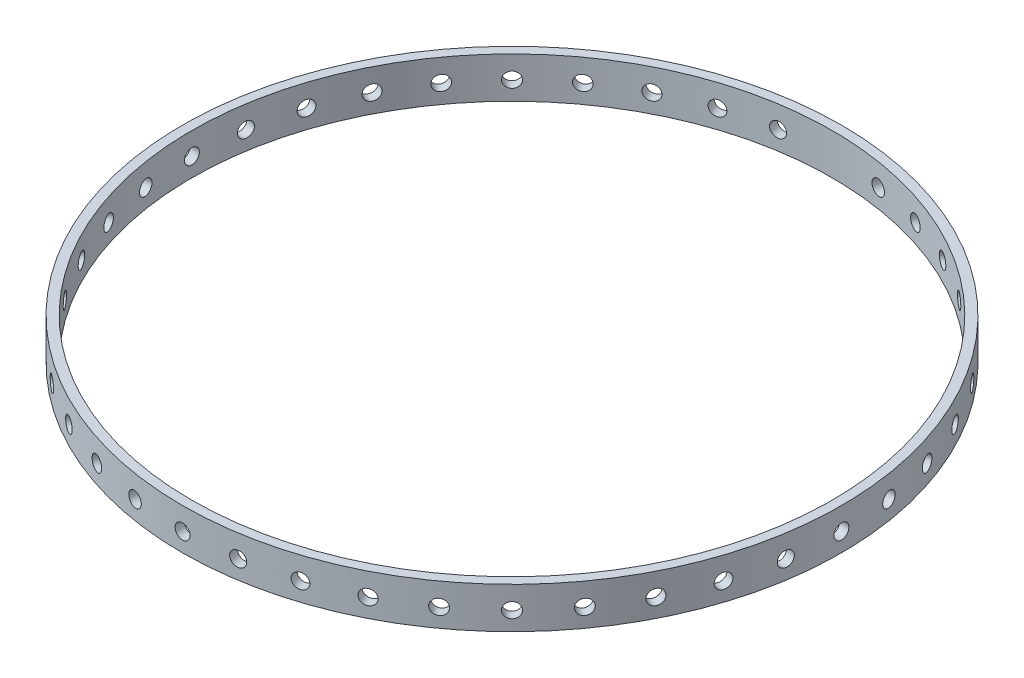
SolidWorks part; units mm, degrees
material "ABS PC"
ref_plane "Front" through (0, 0, 0) normal (0, 0, 1) x (1, 0, 0)
ref_plane "Top" through (0, 0, 0) normal (0, 1, 0) x (1, 0, 0)
ref_plane "Right" through (0, 0, 0) normal (1, 0, 0) x (0, 0, -1)
sketch "Sketch1" plane through (0, 0, 0) normal (0, 1, 0) x (1, 0, 0)
  circle A0 centre (0, 0) radius 85.865
  circle A1 centre (0, 0) radius 88.365
  dimension "D1" = 176.73
  dimension "D2" = 171.73
extrude "Boss-Extrude1" add sketch "Sketch1" along normal blind 11
sketch "Sketch2" plane through (0, 0, 0) normal (0, 0, 1) x (1, 0, 0)
  line L0 (0, 0) -> (0, 5) construction
  circle A0 centre (0, 5) radius 2
  dimension "D2" = 4
  dimension "D1" = 5
extrude "Cut-Extrude1" cut sketch "Sketch2" against normal blind 500
pattern_circular "CirPattern9" count 40 over 360 about axis through (0, 11, 0) along (0, 1, 0) of "Cut-Extrude1", "Boss-Extrude1"
